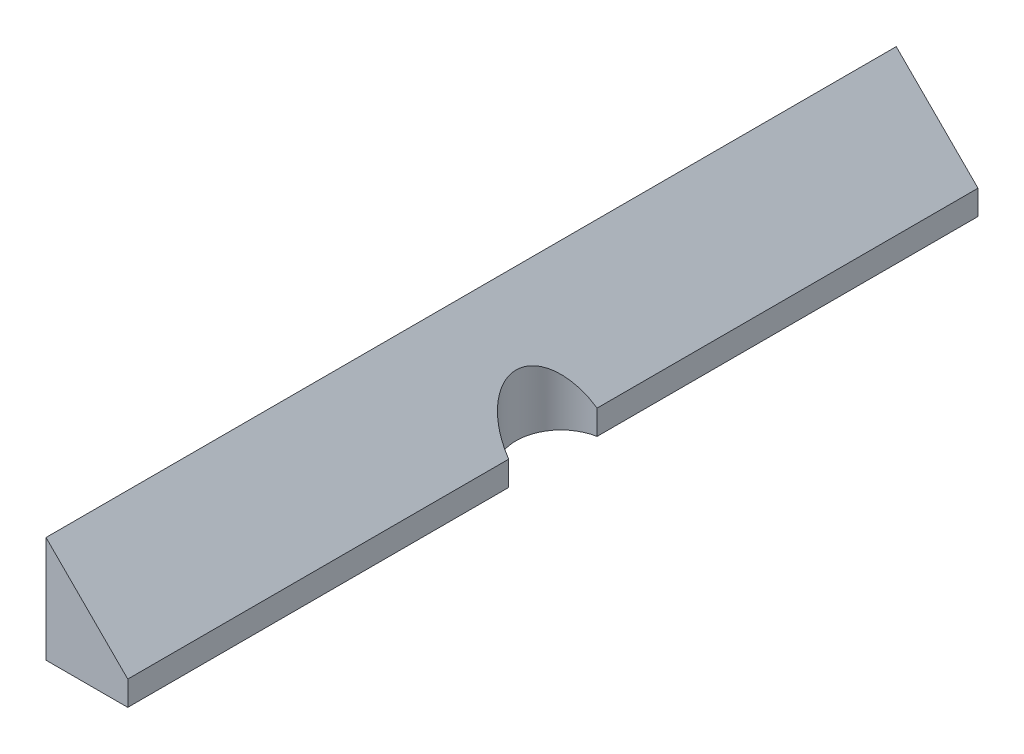
SolidWorks part; units mm, degrees
material "6061-T6 (SS)"
ref_plane "Front Plane" through (0, 0, 0) normal (0, 0, 1) x (1, 0, 0)
ref_plane "Top Plane" through (0, 0, 0) normal (0, 1, 0) x (1, 0, 0)
ref_plane "Right Plane" through (0, 0, 0) normal (1, 0, 0) x (0, 0, -1)
sketch "Sketch1" plane through (0, 0, 0) normal (0, 0, 1) x (1, 0, 0)
  line L5 (0, 0) -> (2.6, 0)
  line L6 (2.6, 0) -> (0, 2.6)
  line L7 (0, 2.6) -> (0, 0)
  line L11 (2, 0) -> (2, 0.6)
  dimension "D1" = 0.6
  dimension "D2" = 2.6
extrude "Boss-Extrude1" add sketch "Sketch1" against normal mid plane 20.8 contours L5 L11 L6 L7 region at (0.7917, 0.9042, 0)
sketch "Sketch2" plane through (0, 0, 0) normal (0, -1, 0) x (1, 0, 0)
  line L0 (2, -10.4) -> (2, 10.4) construction
  circle A12 centre (2.2, 0) radius 1.1
  circle A13 centre (2.2, 22) radius 1.1
  circle A14 centre (2.2, -22) radius 1.1
  dimension "D1" = 2.2
  dimension "D2" = 0.2
  dimension "D3" = 22
  dimension "D4" = 22
extrude "Cut-Extrude1" cut sketch "Sketch2" against normal up to surface (0.4 mm away) up to face at (1, 1.6, 0)
sketch "Sketch3" [suppressed] plane through (0, 0, 0) normal (0, -1, 0) x (1, 0, 0)
  line L1 (2, -20.9183) -> (2, -1.0817) construction
  circle A0 centre (2.2, 0) radius 1
  dimension "D1" = 2
  dimension "D2" = 0.2
extrude "Cut-Extrude2" [suppressed] cut sketch "Sketch3" against normal up to surface (0.4 mm away) up to face at (1.1833, 1.4167, 0)
sketch "Sketch4" [suppressed] plane through (0, 0, 0) normal (0, -1, 0) x (-1, 0, 0)
  line L0 (0, 36.4) -> (0, -36.4) construction
  line L1 (-2, 36.4) -> (0, 36.4)
  line L2 (-2, 36.4) -> (-2, 24.4)
  line L3 (-2, 24.4) -> (0, 24.4)
  line L4 (0, 36.4) -> (0, 24.4)
  dimension "D1" = 12
extrude "Cut-Extrude3" [suppressed] cut sketch "Sketch4" against normal up to vertex up to point (0, 2.6, -10.4)
